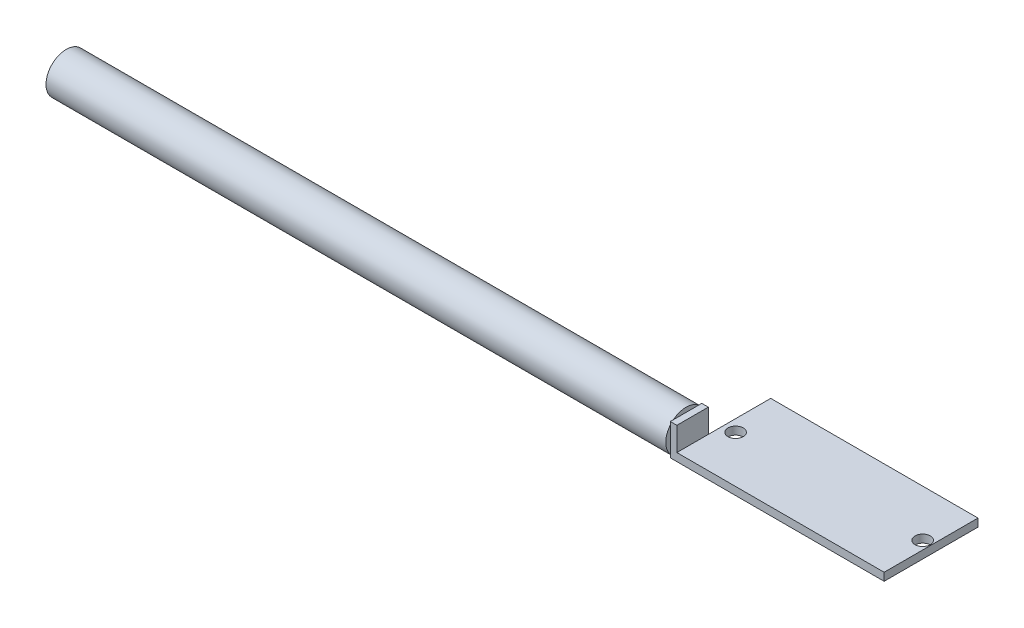
SolidWorks part; units mm, degrees
material "Rubber"
ref_plane "Front Plane" through (0, 0, 0) normal (0, 0, 1) x (1, 0, 0)
ref_plane "Top Plane" through (0, 0, 0) normal (0, 1, 0) x (1, 0, 0)
ref_plane "Right Plane" through (0, 0, 0) normal (1, 0, 0) x (0, 0, -1)
sketch "Sketch1" plane through (0, 0, 0) normal (0, 1, 0) x (1, 0, 0)
  line L1 (-20.066, -9.0869) -> (20.066, -9.0869)
  line L2 (-20.066, -9.0869) -> (-20.066, 9.0868)
  line L3 (-20.066, 9.0868) -> (20.066, 9.0868)
  line L4 (20.066, -9.0869) -> (20.066, 9.0868)
  line L5 (-20.066, -9.0869) -> (20.066, 9.0868) construction
  line L6 (-20.066, 9.0868) -> (20.066, -9.0869) construction
  point P0 (0, 0)
  dimension "D1" = 18.1737
  dimension "D2" = 40.132
extrude "PCB board " add sketch "Sketch1" along normal blind 1.524
sketch "Sketch2" plane through (-20.066, 0, 0) normal (-1, 0, 0) x (0, 0, 1)
  line L1 (9.0869, 0) -> (2.9909, 0)
  line L2 (9.0869, 0) -> (9.0869, 6.096)
  line L3 (9.0869, 6.096) -> (2.9909, 6.096)
  line L4 (2.9909, 0) -> (2.9909, 6.096)
  dimension "D1" = 6.096
  dimension "D2" = 6.096
extrude "Boss-Extrude1" add sketch "Sketch2" along normal blind 1.27
sketch "Sketch3" plane through (-21.336, 0, 0) normal (-1, 0, 0) x (0, 0, 1)
  line L0 (2.9909, 0) -> (9.0869, 6.096) construction
  line L1 (2.9909, 6.096) -> (9.0869, 0) construction
  circle A0 centre (6.0389, 3.048) radius 3.9179
  dimension "D1" = 7.8359
extrude "Boss-Extrude2" add sketch "Sketch3" along normal blind 120
sketch "Sketch4" plane through (0, 1.524, 0) normal (0, 1, 0) x (1, 0, 0)
  line L0 (20.066, -9.0869) -> (20.066, 9.0868) construction
  line L2 (-20.066, 9.0868) -> (-20.066, -2.9909) construction
  circle A0 centre (-17.7768, 0) radius 1.4764
  circle A1 centre (18.4372, 0) radius 1.4764
  point P4 (0, 0)
  dimension "D1" = 2.2892
  dimension "D2" = 2.9527
  dimension "D3" = 1.6288
extrude "Cut-Extrude1" cut sketch "Sketch4" against normal up to surface (1.524 mm away) up to face at (-10.668, 0, 2.2574)
